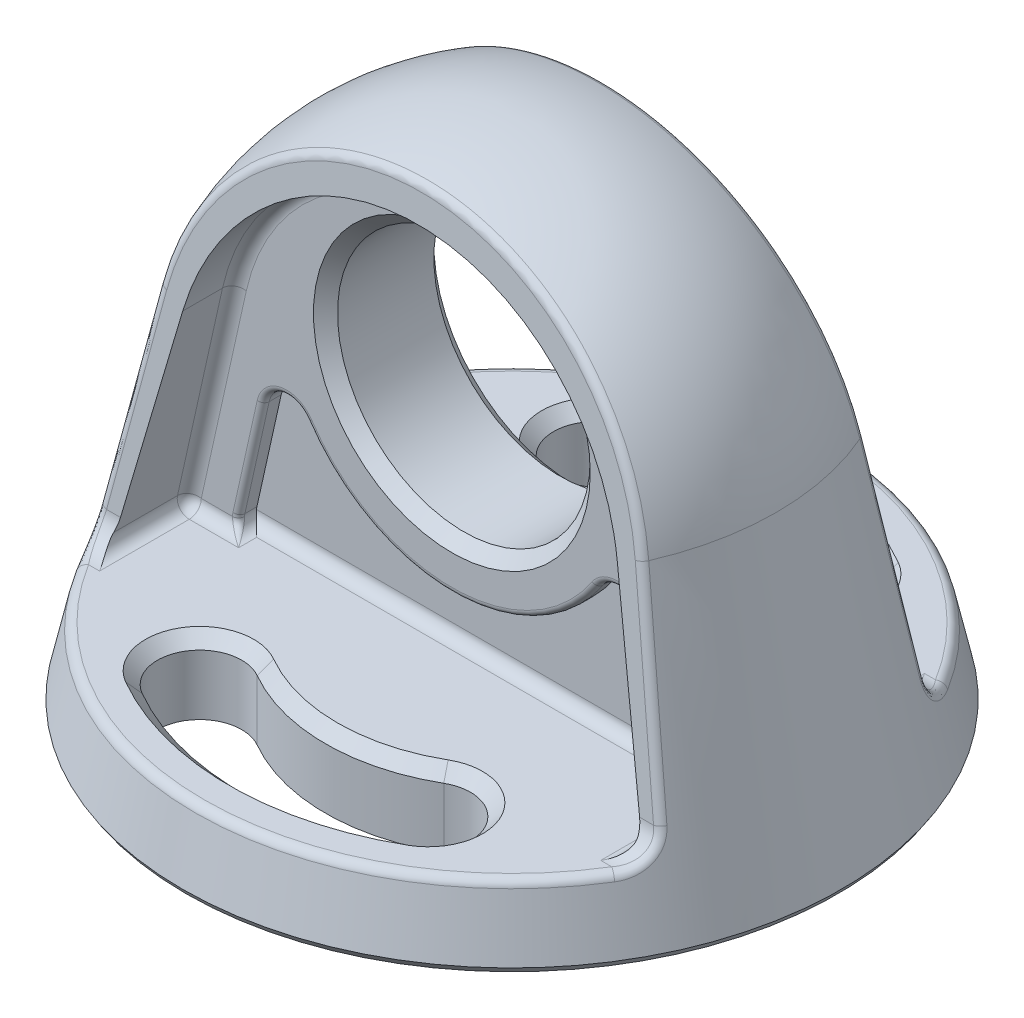
SolidWorks part; units mm, degrees
note: The reader was unsure of these and kept them because the rebuilt part matched: shared geometry of "Sketch4<9>", "Sketch4<10>", "Sketch4<12>", "Sketch4<18>".
ref_plane "Front Plane" through (0, 0, 0) normal (0, 0, 1) x (1, 0, 0)
ref_plane "Top Plane" through (0, 0, 0) normal (0, 1, 0) x (1, 0, 0)
ref_plane "Right Plane" through (0, 0, 0) normal (1, 0, 0) x (0, 0, -1)
sketch "Sketch1" plane through (0, 0, 0) normal (0, 0, 1) x (1, 0, 0)
  line L0 (0, 0) -> (-55, 0)
  line L1 (0, 0) -> (0, 85)
  line L2 (-43.9259, 49.7731) -> (-55, 0)
  arc A0 (0, 85) -> (-43.9259, 49.7731) centre (0, 40) ccw
  dimension "D3" = 45
  dimension "D1" = 55
  dimension "D2" = 85
revolve "Revolve1" add sketch "Sketch1" angle 360 about L1
sketch "Sketch2" plane through (0, 0, 0) normal (1, 0, 0) x (0, 0, -1)
  line L0 (0, 85) -> (0, 0) construction
  line L1 (55, 0) -> (-55, 0)
  line L2 (-55, 0) -> (-52.3301, 12)
  line L3 (-43.9259, 49.7731) -> (-55, 0) construction
  line L4 (-52.3301, 12) -> (-22.4021, 12)
  line L5 (-22.4021, 12) -> (-15, 82.4264)
  line L6 (22.4021, 12) -> (15, 82.4264)
  line L7 (52.3301, 12) -> (22.4021, 12)
  line L8 (55, 0) -> (52.3301, 12)
  arc A0 (43.9259, 49.7731) -> (-43.9259, 49.7731) centre (0, 40) ccw construction
  arc A1 (15, 82.4264) -> (-15, 82.4264) centre (0, 40) ccw
  dimension "D1" = 30
  dimension "D2" = 12
  dimension "D3" = 12
extrude "Cut-Extrude1" cut sketch "Sketch2" against normal through all both and the other way through all flip side to cut contours A1 L5 L4 L2 L1 L8 L7 L6
sketch "Sketch4" plane through (0, 0, 0) normal (0, 0, 1) x (1, 0, 0)
  line L3 (-44.1504, 11.9283) -> (44.1345, 12)
  line L4 (-47.2925, 12) -> (47.2925, 12) construction
  line L5 (47.1909, -1.7374) -> (36.1169, 48.0357)
  line L6 (-36.1169, 48.0357) -> (-47.1909, -1.7374)
  line L7 (44.1345, 12) -> (36.1169, 48.0357)
  line L8 (-36.1169, 48.0357) -> (-44.1504, 11.9283)
  line L9 (-44.1345, 12) -> (44.1345, 12)
  line L11 (-55, 0) -> (55, 0) construction
  line L12 (-55, 0) -> (55, 0)
  line L13 (0, 50) -> (0, 0) construction
  line L14 (-31.3633, 32.5653) -> (-35.9533, 11.935)
  line L15 (31.3633, 32.5653) -> (35.9533, 11.935)
  circle A3 centre (0, 50) radius 21
  arc A4 (36.1169, 48.0357) -> (-36.1169, 48.0357) centre (0, 40) ccw
  arc A5 (36.1169, 48.0357) -> (-36.1169, 48.0357) centre (0, 40) ccw
  arc A6 (-24.1304, 33.9151) -> (24.1304, 33.9151) centre (0, 50) ccw
  arc A7 (31.3633, 32.5653) -> (24.1304, 33.9151) centre (27.4588, 31.6965) ccw
  arc A8 (-24.1304, 33.9151) -> (-31.3633, 32.5653) centre (-27.4588, 31.6965) ccw
  point P25 (28.5793, 45.0781)
  point P28 (-28.5793, 45.0781)
  dimension "D4" = 42
  dimension "D6" = 29
  dimension "D7" = 4
  dimension "D2" = 44.1504
  dimension "D3" = 50
  dimension "D5" = 8
  dimension "D1" = 8
extrude "Cut-Extrude5" cut sketch "Sketch4" against normal through all both and the other way through all contours A3
extrude "Cut-Extrude8" cut sketch "Sketch4<9>" against normal through all from offset 10 offset against normal yes
sketch "Sketch4<9>" plane through (0, 0, 0) normal (0, 0, 1) x (1, 0, 0) same geometry as "Sketch4"
extrude "Cut-Extrude9" cut sketch "Sketch4<10>" along normal through all from offset 10
sketch "Sketch4<10>" plane through (0, 0, 0) normal (0, 0, 1) x (1, 0, 0) same geometry as "Sketch4"
extrude "Cut-Extrude11" cut sketch "Sketch4<12>" along normal through all from offset 7 contours L13 A6 A8 L14 L9 | A6 L13 L9 L15 A7
sketch "Sketch4<12>" plane through (0, 0, 0) normal (0, 0, 1) x (1, 0, 0) same geometry as "Sketch4"
extrude "Cut-Extrude19" cut sketch "Sketch4<18>" against normal through all from offset 7 contours A6 L13 L9 L15 A7 | L13 A6 A8 L14 L9 offset against normal yes
sketch "Sketch4<18>" plane through (0, 0, 0) normal (0, 0, 1) x (1, 0, 0) same geometry as "Sketch4"
sketch "Sketch6" plane through (0, 12, 0) normal (0, 1, 0) x (1, 0, 0)
  line L0 (19, 32.909) -> (0, 0) construction
  line L1 (0, 38) -> (0, 0)
  line L2 (-19, 32.909) -> (0, 0) construction
  line L3 (-38, 0) -> (0, 0) construction
  circle A0 centre (0, 0) radius 38 construction
  arc A1 (19, 32.909) -> (-19, 32.909) centre (0, 0) ccw construction
  arc A6 (22.5, 38.9711) -> (-22.5, 38.9711) centre (0, 0) ccw
  arc A7 (15.5, 26.8468) -> (-15.5, 26.8468) centre (0, 0) ccw
  arc A8 (15.5, 26.8468) -> (22.5, 38.9711) centre (19, 32.909) ccw
  arc A9 (-22.5, 38.9711) -> (-15.5, 26.8468) centre (-19, 32.909) ccw
  arc A10 (19, -32.909) -> (-19, -32.909) centre (0, 0) cw construction
  arc A11 (22.5, -38.9711) -> (-22.5, -38.9711) centre (0, 0) cw
  arc A12 (15.5, -26.8468) -> (-15.5, -26.8468) centre (0, 0) cw
  arc A13 (15.5, -26.8468) -> (22.5, -38.9711) centre (19, -32.909) cw
  arc A14 (-22.5, -38.9711) -> (-15.5, -26.8468) centre (-19, -32.909) cw
  point P5 (0, 38)
  point P17 (0, -38)
  dimension "D1" = 76
  dimension "D2" = 60
  dimension "D4" = 7
  dimension "D3" = 30
extrude "Cut-Extrude20" cut sketch "Sketch6" against normal through all contours A14 A11 A13 A12 | A6 A9 A7 A8
chamfer "Chamfer1" distance 2 angle 45 9 edges at (0, 12, -31) (25.0622, 12, -29.409) (-25.0622, 12, -29.409) (0, 12, -45) (0, 12, 31) (25.0622, 12, 29.409) (-25.0622, 12, 29.409) (0, 12, 45) (21, 50, 10)
chamfer "Chamfer2" distance 1 angle 45 1 edges at (0, 0, -55) first distance on face at (0, 0, -55)
fillet "Fillet1" radius 5 4 edges at (45.7135, 12, -22.4021) (-45.7135, 12, -22.4021) (45.7135, 12, 22.4021) (-45.7135, 12, 22.4021)
fillet "Fillet2" radius 2 20 edges at (-40.1257, 30.0178, -10) (0, 77, -10) (-40.1257, 30.0178, 10) (0, 77, 10) (-44.1345, 12, -18.4521) (-40.0367, 12, -10) (-35.9389, 12, -8.5) (44.1345, 12, -18.4521) (40.0367, 12, -10) (35.9389, 12, -8.5) (0, 12, -7) (40.1257, 30.0178, -10) (35.9389, 12, 8.5) (-35.9389, 12, 8.5) (-40.0367, 12, 10) (40.0367, 12, 10) (-44.1345, 12, 18.4521) (44.1345, 12, 18.4521) (0, 12, 7) (40.1257, 30.0178, 10)
fillet "Fillet3" radius 1.5 12 edges at (46.5228, 13.7714, 23.0862) (0, 82.4264, 15) (-46.3729, 13.1821, 23.6756) (46.3729, 13.1821, -23.6756) (0, 82.4264, -15) (-46.5228, 13.7714, -23.0862) (0, 12, 52.3301) (0, 12, -52.3301)
fillet "Fillet4" radius 1 18 edges at (-34.8592, 12.5858, -10.5858) (-35.433, 14.2185, -10) (-33.3803, 23.4998, -10) (-28.1926, 35.6286, -10) (34.8592, 12.5858, -10.5858) (35.433, 14.2185, -10) (33.3803, 23.4998, -10) (28.1926, 35.6286, -10) (-34.8592, 12.5858, 10.5858) (-35.433, 14.2185, 10) (-33.3803, 23.4998, 10) (-28.1926, 35.6286, 10) (34.8592, 12.5858, 10.5858) (35.433, 14.2185, 10) (33.3803, 23.4998, 10) (28.1926, 35.6286, 10) (0, 21, -10) (0, 21, 10)
chamfer "Chamfer3" distance 2 angle 45 1 edges at (21, 50, -10)
